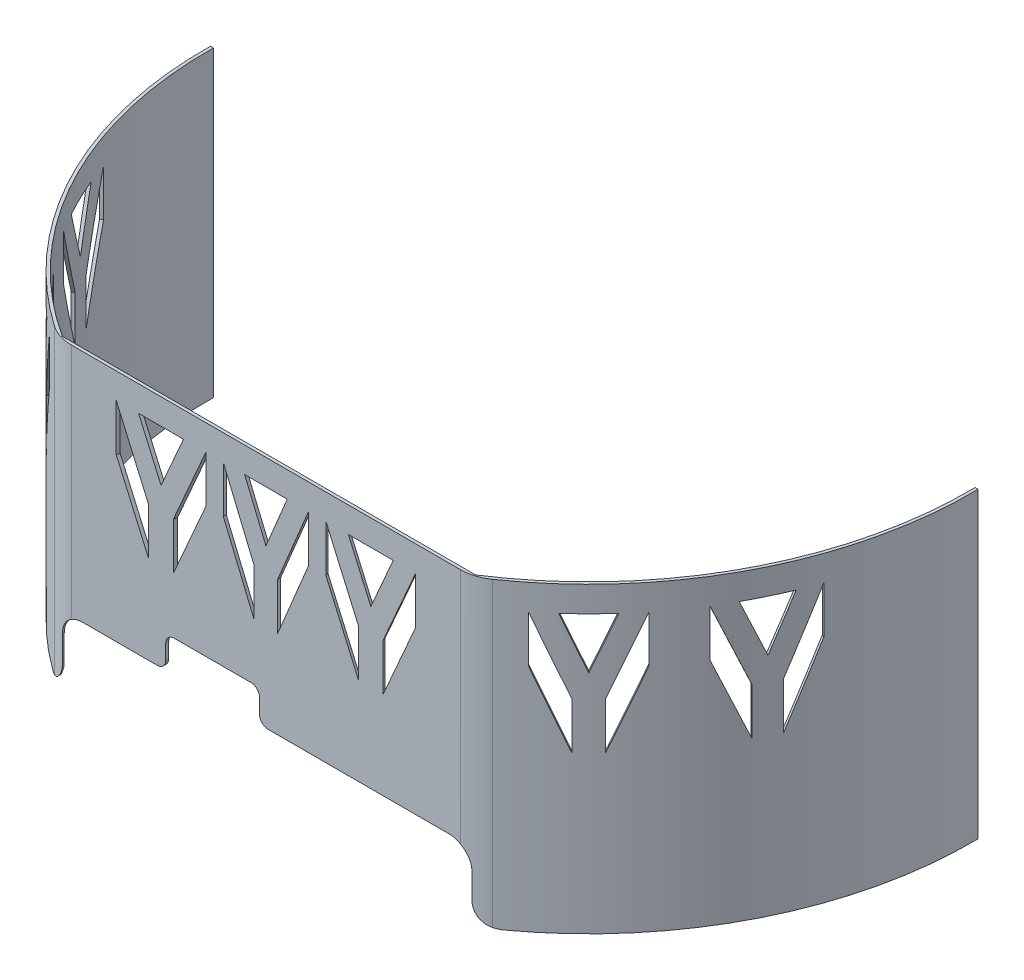
SolidWorks part; units mm, degrees
ref_plane "Front Plane" through (0, 0, 0) normal (0, 0, 1) x (1, 0, 0)
ref_plane "Top Plane" through (0, 0, 0) normal (0, 1, 0) x (1, 0, 0)
ref_plane "Right Plane" through (0, 0, 0) normal (1, 0, 0) x (0, 0, -1)
sketch "Sketch1" plane through (0, 0, 0) normal (0, 1, 0) x (1, 0, 0)
  line L0 (0, 124.168) -> (0, -125.7458) construction
  line L1 (-136.0011, 0) -> (148.623, 0) construction
  line L2 (-48.4715, -75) -> (48.4715, -75)
  line L3 (-48.6776, -75.7) -> (48.6776, -75.7)
  arc A0 (48.4715, -75) -> (-48.4715, -75) centre (0, 0) ccw
  arc A1 (48.6776, -75.7) -> (-48.6776, -75.7) centre (0, 0) ccw
  dimension "D1" = 178.6
  dimension "D3" = 180
  dimension "D2" = 75
  dimension "D4" = 75.7
extrude "Boss-Extrude1" add sketch "Sketch1" along normal blind 71
fillet "Fillet1" radius 10 2 edges at (-48.6776, 35.5, 75.7) (48.6776, 35.5, 75.7)
sketch "Sketch2" plane through (0, 0, 75.7) normal (0, 0, 1) x (1, 0, 0)
  line L0 (0, 94.4811) -> (0, -36.6428) construction
  line L1 (45.6455, 0) -> (51.3512, 0) construction
  line L2 (-48, 16) -> (48, 16)
  line L4 (-48, 16) -> (-48, 0)
  line L5 (-48, 0) -> (48, 0)
  line L6 (48, 16) -> (48, 0)
  line L7 (-48, 16) -> (48, 0) construction
  line L8 (-48, 0) -> (48, 16) construction
  line L9 (-45.6455, 71) -> (45.6455, 71) construction
  point P3 (0, 8)
  dimension "D1" = 55
  dimension "D2" = 96
extrude "Cut-Extrude1" cut sketch "Sketch2" against normal blind 5
sketch "Sketch3" plane through (0, 0, 75.7) normal (0, 0, 1) x (1, 0, 0)
  line L0 (0, 94.4811) -> (0, -26.607) construction
  line L1 (45.6455, 16) -> (-45.6455, 16) construction
  line L2 (-23.5, 16) -> (-1.5, 16)
  line L3 (-23.5, 16) -> (-23.5, 23.5)
  line L4 (-23.5, 23.5) -> (-1.5, 23.5)
  line L5 (-1.5, 16) -> (-1.5, 23.5)
  dimension "D1" = 22
  dimension "D2" = 7.5
  dimension "D3" = 1.5
extrude "Cut-Extrude2" cut sketch "Sketch3" against normal blind 5
fillet "Fillet2" radius 5 4 edges at (-48, 16, 75.2094) (-48, 0, 75.2094) (48, 16, 75.2094) (48, 0, 75.2094)
fillet "Fillet3" radius 2 4 edges at (-1.5, 16, 75.35) (-1.5, 23.5, 75.35) (-23.5, 16, 75.35) (-23.5, 23.5, 75.35)
sketch "Sketch4" plane through (0, 0, 0) normal (0, 0, 1) x (1, 0, 0)
  line L0 (0, 103.2008) -> (0, -37.4655) construction
  line L1 (-5, 65) -> (5, 65)
  line L2 (-5, 65) -> (0, 53)
  line L3 (0, 53) -> (5, 65)
  line L8 (-45.6455, 71) -> (45.6455, 71) construction
  line L9 (-10, 65) -> (-2.75, 47.6)
  line L10 (-2.75, 47.6) -> (-2.75, 36.6)
  line L11 (-2.75, 36.6) -> (-10, 54)
  line L12 (-10, 54) -> (-10, 65)
  line L13 (10, 65) -> (2.75, 47.6)
  line L14 (2.75, 47.6) -> (2.75, 36.6)
  line L15 (2.75, 36.6) -> (10, 54)
  line L16 (10, 54) -> (10, 65)
  point P6 (0, 65)
  dimension "D1" = 10
  dimension "D2" = 6
  dimension "D3" = 5
  dimension "D4" = 11
  dimension "D5" = 12
  dimension "D6" = 2.75
extrude "Cut-Extrude3" cut sketch "Sketch4" against normal blind 132
pattern_circular "CirPattern1" count 20 over 360 about axis through (0, 71, 0) along (0, 1, 0) skipping 1, 2, 3, 4, 5, 6, 7, 8, 12, 13, 14, 15, 16, 17, 18, 19 of "Cut-Extrude3"
pattern_circular "CirPattern2" count 16 over 360 about axis through (0, 71, 0) along (0, 1, 0) of "Cut-Extrude3"
pattern_circular "CirPattern3" count 28 over 360 about axis through (0, 71, 0) along (0, 1, 0) of "Cut-Extrude3"
sketch "Sketch6" plane through (0, 0, 0) normal (0, 1, 0) x (1, 0, 0)
  line L0 (-100.8658, 1.3) -> (109.8927, 1.3) construction
  line L1 (-45.6455, -75.7) -> (45.6455, -75.7) construction
  line L3 (-100.8658, 1.3) -> (109.8927, 1.3)
  line L4 (-100.8658, 1.3) -> (-100.8658, 95.751)
  line L5 (-100.8658, 95.751) -> (109.8927, 95.751)
  line L6 (109.8927, 1.3) -> (109.8927, 95.751)
  dimension "D1" = 77
extrude "Cut-Extrude4" cut sketch "Sketch6" along normal blind 92
ref_plane "Plane1" through (89.3, 0, 0) normal (-1, 0, 0) x (0, 0, 1)
ref_plane "Plane2" through (-89.3, 0, 0) normal (1, 0, 0) x (0, 0, -1)
sketch "Sketch9" plane through (0, 0, 0) normal (0, 1, 0) x (1, 0, 0)
  line L0 (-75.6116, -47.5118) -> (0, 0) construction
  line L1 (-69.8185, -55.6764) -> (0, 0) construction
